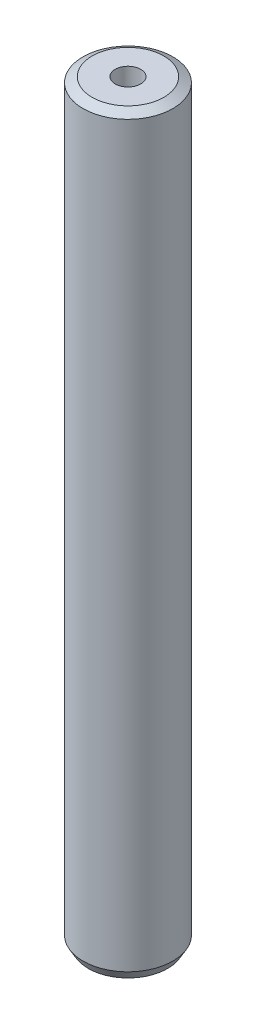
SolidWorks part; units mm, degrees
ref_plane "Front Plane" through (0, 0, 0) normal (0, 0, 1) x (1, 0, 0)
ref_plane "Top Plane" through (0, 0, 0) normal (0, 1, 0) x (1, 0, 0)
ref_plane "Right Plane" through (0, 0, 0) normal (1, 0, 0) x (0, 0, -1)
sketch "Sketch1" plane through (0, 0, 0) normal (0, 1, 0) x (1, 0, 0)
  circle A0 centre (0, 0) radius 5
  dimension "SHAFT_OD" = 10
extrude "Boss-Extrude1" add sketch "Sketch1" along normal blind 83.7847
sketch "Sketch2" plane through (0, 0, 0) normal (0, 1, 0) x (1, 0, 0)
  circle A0 centre (0, 0) radius 1.4198
  dimension "BORE_D" = 2.8397
extrude "Cut-Extrude1" cut sketch "Sketch2" along normal through all
chamfer "Chamfer1" distance 0.582 angle 60 2 edges at (0, 83.7847, 5) (0, 0, 5) first distance on face at (0, 83.7847, 5) first distance on face at (0, 0, 1.4198)
